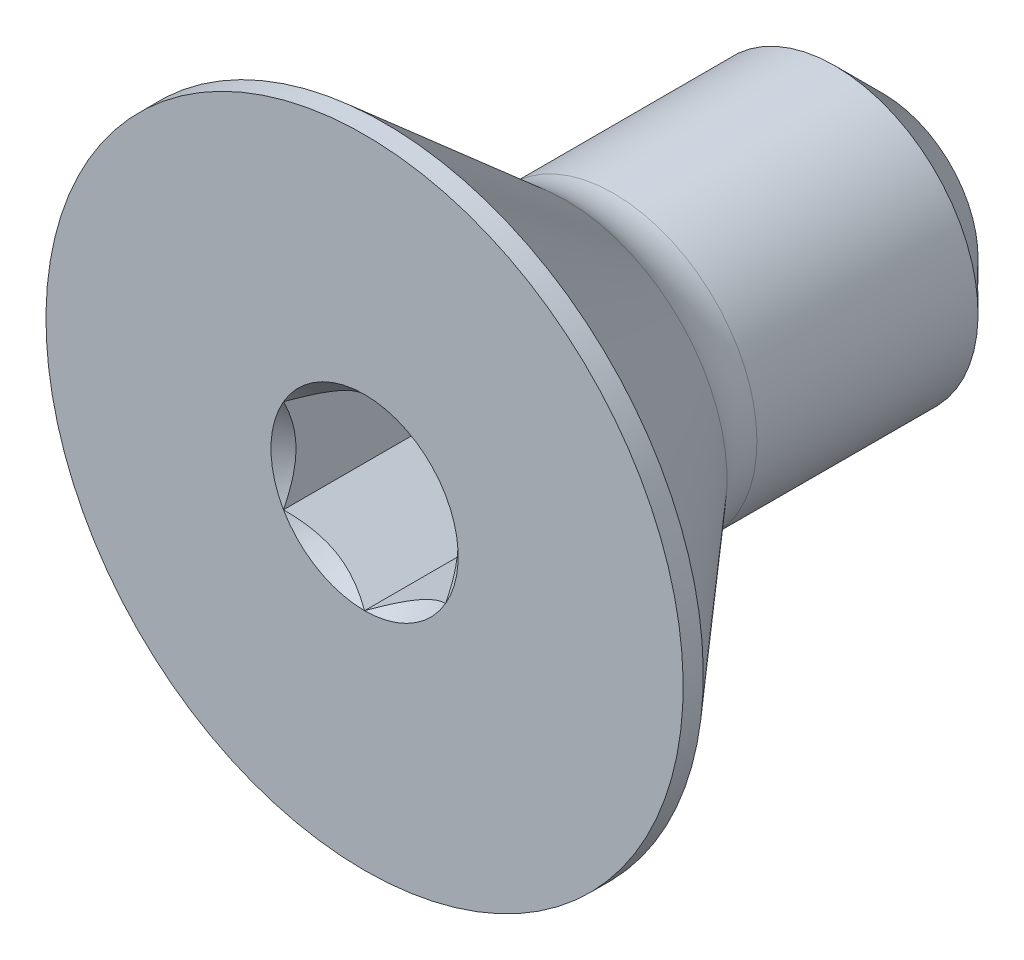
SolidWorks part; units mm, degrees
ref_plane "Front" through (0, 0, 0) normal (0, 0, 1) x (1, 0, 0)
ref_plane "Top" through (0, 0, 0) normal (0, 1, 0) x (1, 0, 0)
ref_plane "Right" through (0, 0, 0) normal (1, 0, 0) x (0, 0, -1)
sketch "Sketch1" plane through (0, 0, 0) normal (1, 0, 0) x (0, 0, -1)
  line L0 (-3.175, 3.8989) -> (-2.9286, 3.8989) construction
  line L1 (-2.9286, 3.8989) -> (-0.7112, 1.9713) construction
  line L2 (-3.175, 1.7526) -> (3.175, 1.7526)
  line L3 (3.175, 1.7526) -> (3.175, 0)
  line L4 (3.175, 0) -> (-3.175, 0)
  line L5 (-3.175, 0) -> (-3.175, 3.8989) construction
  line L6 (-3.175, 3.8989) -> (-3.175, -3.8989) construction
  line L7 (3.175, 1.7526) -> (3.175, -1.7526) construction
  line L8 (-3.175, -3.8989) -> (-2.9286, -3.8989) construction
  line L9 (-2.9286, -3.8989) -> (-0.7112, -1.9713) construction
  line L11 (-3.175, 1.7526) -> (-3.175, 0)
  line L12 (-0.7112, 1.9713) -> (-0.7112, 0) construction
  line L14 (3.175, -1.7526) -> (2.3812, -1.7526) construction
  line L15 (-3.175, 0.9922) -> (-3.175, -0.9922)
  arc A2 (-0.7112, 1.9713) -> (-0.1262, 1.7526) centre (-0.1262, 2.6443) ccw construction
  point P18 (0, 0)
  point P19 (-0.2886, -1.7526)
  point P24 (-3.175, 0)
  dimension "Head Diameter" = 7.7978
  dimension "Screw Size Decimal Equivalent" = 3.5052
  dimension "Head Height" = 2.4638
  dimension "Countersink Angle" = 82
  dimension "Thread Pitch" = 0.7937
  dimension "D2" = 3.4636
  dimension "Drive Size" = 1.9844
  dimension "Length" = 6.35
  dimension "D1" = 0.2464
sketch "Sketch12" plane through (0, 0, 0) normal (1, 0, 0) x (0, 0, -1)
  line L0 (3.175, 1.7526) -> (3.175, 0) construction
  line L1 (-3.175, 1.7526) -> (3.175, 1.7526) construction
  line L2 (-3.175, 1.7526) -> (-3.175, 0) construction
  line L3 (3.175, 0) -> (-3.175, 0) construction
  line L4 (3.175, 1.7526) -> (3.175, 0)
  line L5 (-3.175, 1.7526) -> (3.175, 1.7526)
  line L6 (-3.175, 1.7526) -> (-3.175, 0)
  line L7 (3.175, 0) -> (-3.175, 0)
revolve "Revolve3" add sketch "Sketch12" angle 360 about L7
sketch "Sketch3" [suppressed] plane through (0, 0, -3.175) normal (0, 0, -1) x (-1, 0, 0)
  circle A0 centre (0, 0) radius 1.7526
sketch "Sketch7" plane through (0, 0, 0) normal (1, 0, 0) x (0, 0, -1)
  line L0 (-3.175, 3.8989) -> (-2.9286, 3.8989) construction
  line L1 (-2.9286, 3.8989) -> (-0.7112, 1.9713) construction
  line L2 (-3.175, 3.8989) -> (-2.9286, 3.8989)
  line L3 (-2.9286, 3.8989) -> (-0.7112, 1.9713)
  line L6 (-0.1262, 1.7526) -> (-0.1262, 0)
  line L7 (-3.175, 0) -> (-3.175, 3.8989) construction
  line L8 (-3.175, 0) -> (-3.175, 3.8989)
  line L9 (-3.175, 0) -> (-0.1262, 0)
  line L10 (14.3708, 0) -> (-14.3708, 0) construction
  arc A0 (-0.7112, 1.9713) -> (-0.1262, 1.7526) centre (-0.1262, 2.6443) ccw construction
  arc A1 (-0.7112, 1.9713) -> (-0.1262, 1.7526) centre (-0.1262, 2.6443) ccw
revolve "Revolve2" add sketch "Sketch7" angle 360 mid plane about L9
chamfer "Chamfer1" distance 0.5953 angle 45 1 edges at (0, 1.7526, -3.175)
sketch "Sketch5" plane through (0, 0, 3.175) normal (0, 0, 1) x (1, 0, 0)
  line L0 (0, 0) -> (-1.1457, 0) construction
  line L1 (0, 0) -> (-2.7496, 1.5875) construction
  line L2 (0, 0) -> (-2.7496, -1.5875) construction
  line L6 (0, 1.1457) -> (0, 0.9449) construction
  line L7 (0, 0.9449) -> (0, 0.7441) construction
  line L9 (0, 1.1457) -> (-0.9922, 0.5728)
  line L10 (-0.9922, 0.5728) -> (-0.9922, -0.5728)
  line L11 (-0.9922, -0.5728) -> (0, -1.1457)
  line L12 (0, -1.1457) -> (0.9922, -0.5728)
  line L13 (0.9922, -0.5728) -> (0.9922, 0.5728)
  line L14 (0.9922, 0.5728) -> (0, 1.1457)
  circle A0 centre (0, 0) radius 1.1457 construction
  circle A1 centre (0, 0) radius 0.9449 construction
  circle A2 centre (0, 0) radius 0.7441 construction
  circle A3 centre (0, 0) radius 0.9922 construction
  dimension "D3" = 1.4883
  dimension "D4" = 30
  dimension "D5" = 30
  dimension "Hex" = 1.9844
extrude "Cut-Extrude2" cut sketch "Sketch5" against normal blind 1.7247
sketch "Sketch6" plane through (0, 0, 3.175) normal (0, 0, 1) x (1, 0, 0)
  circle A0 centre (0, 0) radius 1.1457
extrude "Cut-Extrude3" cut sketch "Sketch6" against normal blind 1.7247 draft 45
ref_plane "Plane3" [suppressed] through (0, 0, 0.1262) normal (0, 0, 1) x (1, 0, 0)
split "Split1" [suppressed] bodies to split 135
curve "Helix/Spiral1" [suppressed] pitch 0.7937 height 7.1437 turns 9
sketch "Sketch2" [suppressed] plane through (0, 0, 0) normal (1, 0, 0) x (0, 0, -1)
  line L0 (3.1254, 1.8385) -> (3.5223, 1.1511) construction
  line L1 (3.5223, 1.1511) -> (3.9191, 1.8385) construction
  line L2 (3.9191, 1.8385) -> (3.1254, 1.8385) construction
  line L3 (3.5223, 1.1511) -> (3.5223, 1.237) construction
  line L4 (3.4727, 1.237) -> (3.5719, 1.237)
  line L5 (3.5223, 1.7526) -> (3.5223, 1.8385) construction
  line L6 (3.175, 1.7526) -> (3.8695, 1.7526) construction
  line L7 (3.175, -1.7526) -> (2.3812, -1.7526) construction
  line L8 (3.4727, 1.237) -> (3.1502, 1.7956)
  line L9 (3.1502, 1.7956) -> (3.8943, 1.7956)
  line L10 (3.8943, 1.7956) -> (3.5719, 1.237)
  point P15 (3.5223, 1.7956)
  dimension "D1" = 0.0992
sweep "Cut-Sweep1" [suppressed] cut profiles "Sketch2" path "Helix/Spiral1"
sketch "Sketch13" [suppressed] plane through (0, 0, 0.1262) normal (0, 0, 1) x (1, 0, 0)
  circle A2 centre (0, 0) radius 1.7526
  circle A4 centre (0, 0) radius 1.7526
  dimension "D1" = 0
extrude "Boss-Extrude3" [suppressed] add sketch "Sketch13" against normal up to next draft 60
equation "\"D3@Helix/Spiral1\"=\"Length@Sketch1\"+\"Thread Pitch@Sketch1\""
equation "\"D1@Chamfer1\" = \"D4@Helix/Spiral1\" * .75"
equation "\"D1@Cut-Extrude2\" = \"Head Height@Sketch1\" * .7"
equation "\"D1@Cut-Extrude3\" = \"D1@Cut-Extrude2\""
equation "\"D3@Sketch5\" = \"Hex@Sketch5\" * .75"
equation "\"D4@Helix/Spiral1\"=\"Thread Pitch@Sketch1\""
equation "\"Hex@Sketch5\"=\"Drive Size@Sketch1\""
equation "\"D1@Sketch2\"=\"Thread Pitch@Sketch1\"*0.125"
equation "\"D1@Sketch1\"=\"Head Height@Sketch1\"*.1"
